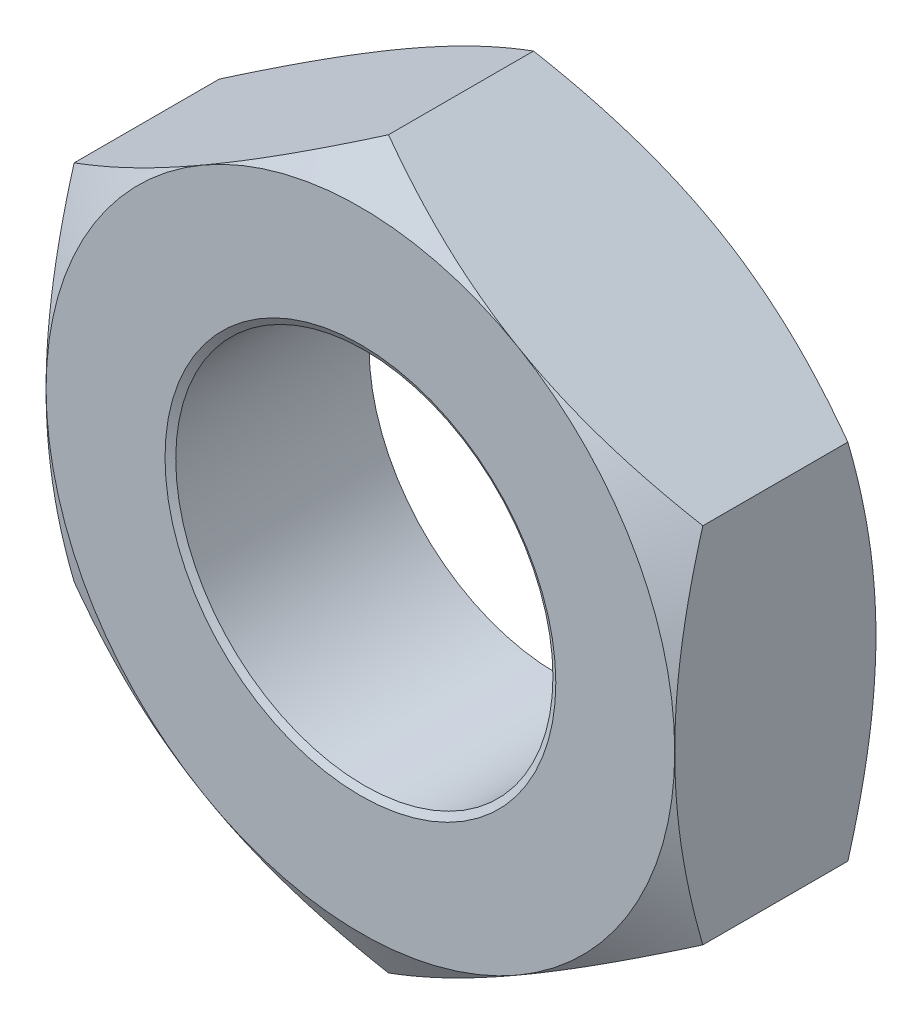
SolidWorks part; units mm, degrees
material "Chrome Stainless Steel"
ref_plane "Front Plane" through (0, 0, 0) normal (0, 0, 1) x (1, 0, 0)
ref_plane "Top Plane" through (0, 0, 0) normal (0, 1, 0) x (1, 0, 0)
ref_plane "Right Plane" through (0, 0, 0) normal (1, 0, 0) x (0, 0, -1)
sketch "Sketch1" plane through (0, 0, 0) normal (0, 0, 1) x (1, 0, 0)
  line L1 (0, 5.7735) -> (-5, 2.8868)
  line L2 (-5, 2.8868) -> (-5, -2.8868)
  line L3 (-5, -2.8868) -> (0, -5.7735)
  line L4 (0, -5.7735) -> (5, -2.8868)
  line L5 (5, -2.8868) -> (5, 2.8868)
  line L6 (5, 2.8868) -> (0, 5.7735)
  circle A0 centre (0, 0) radius 5 construction
  circle A1 centre (0, 0) radius 3
  point P1 (0, 3)
  point P11 (3, 0)
  dimension "Thread Size" = 6
  dimension "HexWIdth" = 10
sketch "Sketch2" plane through (0, 0, 0) normal (1, 0, 0) x (0, 0, -1)
  line L0 (1.6, 0) -> (-1.6, 0) construction
  line L1 (-1.6, -3) -> (-1.6, 3) construction
  line L8 (-2.5375, 3.1083) -> (-1.5375, 3.1083) construction
  line L9 (-1.5375, 3.1083) -> (-2.0375, 2.2422) construction
  line L10 (-2.0375, 2.2422) -> (-2.5375, 3.1083) construction
  line L11 (-2.475, 3) -> (-1.6, 3) construction
  line L12 (-2.1, 2.3505) -> (-1.975, 2.3505) construction
  line L13 (-2.0375, 2.2422) -> (-2.0375, 2.3505) construction
  line L14 (-2.0375, 3) -> (-2.0375, 3.1083) construction
  line L15 (-2.5063, 3.0541) -> (-1.5688, 3.0541)
  line L16 (-1.5688, 3.0541) -> (-1.975, 2.3505)
  line L17 (-1.975, 2.3505) -> (-2.1, 2.3505)
  line L18 (-2.1, 2.3505) -> (-2.5063, 3.0541)
  point P4 (0, 0)
  point P8 (-1.6, 0)
  point P23 (-2.0375, 3.0541)
  dimension "Height" = 3.2
  dimension "Pitch" = 1
  dimension "D1" = 0.125
sketch "Sketch3" plane through (0, 0, 0) normal (0, 0, 1) x (1, 0, 0)
  line L0 (-5, 2.8868) -> (-5, -2.8868) construction
  line L1 (-5, -2.8868) -> (0, -5.7735) construction
  line L2 (0, -5.7735) -> (5, -2.8868) construction
  line L3 (5, -2.8868) -> (5, 2.8868) construction
  line L4 (5, 2.8868) -> (0, 5.7735) construction
  line L5 (0, 5.7735) -> (-5, 2.8868) construction
  line L6 (-5, 2.8868) -> (-5, -2.8868)
  line L7 (-5, -2.8868) -> (0, -5.7735)
  line L8 (0, -5.7735) -> (5, -2.8868)
  line L9 (5, -2.8868) -> (5, 2.8868)
  line L10 (5, 2.8868) -> (0, 5.7735)
  line L11 (0, 5.7735) -> (-5, 2.8868)
  circle A0 centre (0, 0) radius 3 construction
  circle A1 centre (0, 0) radius 3
extrude "Boss-Extrude1" add sketch "Sketch3" along normal mid plane 3.2
sketch "Sketch4" plane through (0, 0, 1.6) normal (0, 0, 1) x (1, 0, 0)
  circle A0 centre (0, 0) radius 5 construction
  circle A1 centre (0, 0) radius 5
  circle A2 centre (0, 0) radius 3.1083
extrude "Cut-Extrude1" cut sketch "Sketch4" against normal blind 10 draft 60 flip side to cut
mirror "Mirror1" about plane through (0, 0, 0) normal (0, 0, 1) of "Cut-Extrude1"
sketch "Sketch6" [suppressed] plane through (0, 0, 1.6) normal (0, 0, 1) x (1, 0, 0)
  circle A0 centre (0, 0) radius 3 construction
  circle A1 centre (0, 0) radius 3
ref_axis "Center Axis" through (0, 0, 1.5375) along (0, 0, -1)
curve "Helix/Spiral1" [suppressed] pitch 1 height 4.2 turns 4.2
sketch "Sketch7" [suppressed] plane through (0, 0, 0) normal (1, 0, 0) x (0, 0, -1)
  line L0 (-2.5063, 3.0541) -> (-1.5688, 3.0541) construction
  line L1 (-1.5688, 3.0541) -> (-1.975, 2.3505) construction
  line L2 (-1.975, 2.3505) -> (-2.1, 2.3505) construction
  line L3 (-2.1, 2.3505) -> (-2.5063, 3.0541) construction
  line L4 (-2.5063, 3.0541) -> (-1.5688, 3.0541)
  line L5 (-1.5688, 3.0541) -> (-1.975, 2.3505)
  line L6 (-1.975, 2.3505) -> (-2.1, 2.3505)
  line L7 (-2.1, 2.3505) -> (-2.5063, 3.0541)
sweep "Sweep1" [suppressed] add profiles "Sketch7" path "Helix/Spiral1"
sketch "Sketch8" [suppressed] plane through (0, 0, 1.6) normal (0, 0, 1) x (1, 0, 0)
  circle A0 centre (0, 0) radius 3.1083 construction
  circle A1 centre (0, 0) radius 3.1083
extrude "Cut-Extrude2" [suppressed] cut sketch "Sketch8" against normal blind 10 draft 60 and the other way through all
mirror "Mirror2" [suppressed] about plane through (0, 0, 0) normal (0, 0, 1)
equation "\"D1@Sketch2\"=\"Pitch@Sketch2\"/8"
equation "\"D1@Boss-Extrude1\"=\"Height@Sketch2\""
equation "\"D4@Helix/Spiral1\"=\"Pitch@Sketch2\""
equation "\"D3@Helix/Spiral1\"=\"Height@Sketch2\"+\"D4@Helix/Spiral1\""
